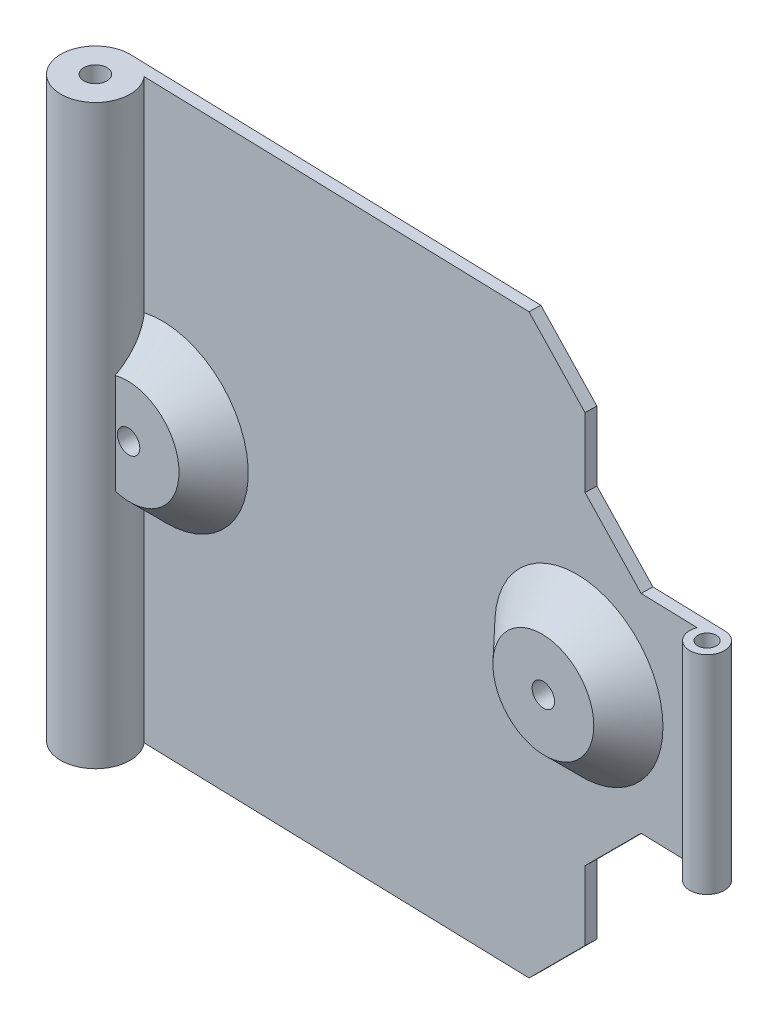
SolidWorks part; units mm, degrees
ref_plane "Front Plane" through (0, 0, 0) normal (0, 0, 1) x (1, 0, 0)
ref_plane "Top Plane" through (0, 0, 0) normal (0, 1, 0) x (1, 0, 0)
ref_plane "Right Plane" through (0, 0, 0) normal (1, 0, 0) x (0, 0, -1)
sketch "Sketch1" plane through (0, 0, 0) normal (0, 1, 0) x (1, 0, 0)
  circle A0 centre (0, 0) radius 3
  circle A1 centre (53, 0) radius 1.5
  circle A2 centre (53, 0) radius 0.8
  circle A3 centre (0, 0) radius 1
  dimension "D2" = 6
  dimension "D3" = 3
  dimension "D4" = 2
  dimension "D5" = 1.6
  dimension "D1" = 53
extrude "Boss-Extrude1" add sketch "Sketch1" along normal blind 50
sketch "Sketch2" plane through (0, 50, 0) normal (0, 1, 0) x (1, 0, 0)
  line L0 (0, 3) -> (53, 1.5)
  circle A2 centre (0, 0) radius 3 construction
  circle A3 centre (53, 0) radius 1.5 construction
extrude "Extrude-Thin1" add sketch "Sketch2" against normal blind 50 thin thin type one direction wall 1
sketch "Sketch3" plane through (0.0278, 0, -1.9988) normal (-0.0283, 0, 0.9996) x (0.9996, 0, 0.0283)
  line L0 (2.958, 25) -> (51.134, 25) construction
  line L1 (2.958, 0) -> (2.958, 50) construction
  line L2 (51.134, 0) -> (51.134, 50) construction
  circle A0 centre (4.046, 25) radius 2.5
  circle A1 centre (41.046, 25) radius 2.5
  circle A2 centre (4.046, 25) radius 1
  circle A3 centre (41.046, 25) radius 1
  point P10 (27.046, 25)
  dimension "D1" = 37
  dimension "D3" = 5
  dimension "D4" = 2
  dimension "D2" = 23
extrude "Boss-Extrude2" add sketch "Sketch3" along normal blind 3
chamfer "Chamfer1" distance 5 angle 45 2 edges at (43.5563, 25, -0.7669) (6.5712, 25, -1.8136)
sketch "Sketch4" plane through (0.0565, 0, -1.998) normal (-0.0283, 0, 0.9996) x (0.9996, 0, 0.0283)
  line L0 (2.2371, 50) -> (51.5644, 50) construction
  line L1 (41.5644, 50) -> (56.917, 50)
  line L2 (41.5644, 50) -> (41.5644, 34)
  line L3 (41.5644, 34) -> (56.917, 34)
  line L4 (56.917, 50) -> (56.917, 34)
  line L5 (2.2371, 0) -> (51.5644, 0) construction
  line L6 (41.5644, 0) -> (59.0354, 0)
  line L7 (41.5644, 0) -> (41.5644, 16)
  line L8 (41.5644, 16) -> (59.0354, 16)
  line L9 (59.0354, 0) -> (59.0354, 16)
  line L10 (51.5644, 0) -> (51.5644, 50) construction
  dimension "D1" = 16
  dimension "D2" = 16
  dimension "D3" = 10
extrude "Cut-Extrude1" cut sketch "Sketch4" against normal through all both and the other way through all
chamfer "Chamfer2" distance 5 angle 45 4 edges at (41.6184, 0, -1.3219) (41.6184, 16, -1.3219) (41.6184, 34, -1.3219) (41.6184, 50, -1.3219)
sketch "Sketch5" plane through (0, 34, 0) normal (0, 1, 0) x (1, 0, 0)
  circle A0 centre (53, 0) radius 0.8
extrude "Cut-Extrude2" cut sketch "Sketch5" against normal blind 28
